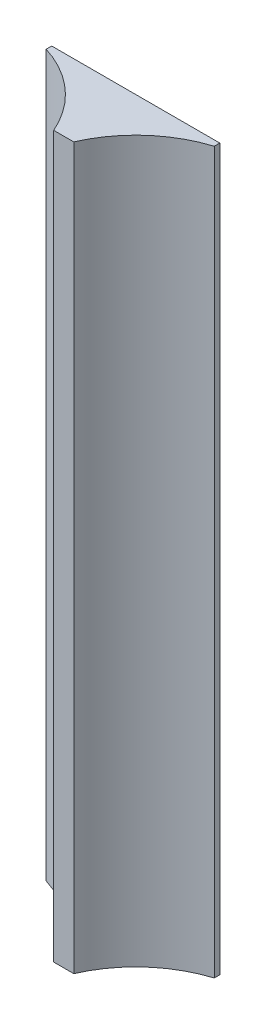
SolidWorks part; units mm, degrees
ref_plane "Front" through (0, 0, 0) normal (0, 0, 1) x (1, 0, 0)
ref_plane "Top" through (0, 0, 0) normal (0, 1, 0) x (1, 0, 0)
ref_plane "Right" through (0, 0, 0) normal (1, 0, 0) x (0, 0, -1)
sketch "Sketch1" plane through (0, 0, 0) normal (0, 1, 0) x (1, 0, 0)
  line L0 (-0.8348, 0) -> (0.8348, 0)
  line L1 (7, 5.5394) -> (7, 6)
  line L2 (7, 6) -> (-7, 6)
  line L3 (-7, 6) -> (-7, 5.5394)
  arc A0 (0.8348, 0) -> (7, 5.5394) centre (10, -4) cw
  arc A1 (-7, 5.5394) -> (-0.8348, 0) centre (-10, -4) cw
  point P9 (0, 6)
  point P10 (0, 0)
  dimension "D1" = 10
  dimension "D6" = 6
  dimension "D2" = 20
  dimension "D3" = 10
  dimension "D4" = 14
extrude "Boss-Extrude1" add sketch "Sketch1" along normal blind 60
sketch "Sketch3" plane through (0, 0, -6) normal (0, 0, -1) x (-1, 0, 0)
  line L0 (0, 0) -> (0, 60) construction
  line L1 (-7, 0) -> (7, 0) construction
  line L2 (-7, 60) -> (7, 60) construction
  point P6 (0, 45)
  point P7 (0, 15)
  dimension "D1" = 15
  dimension "D2" = 15
